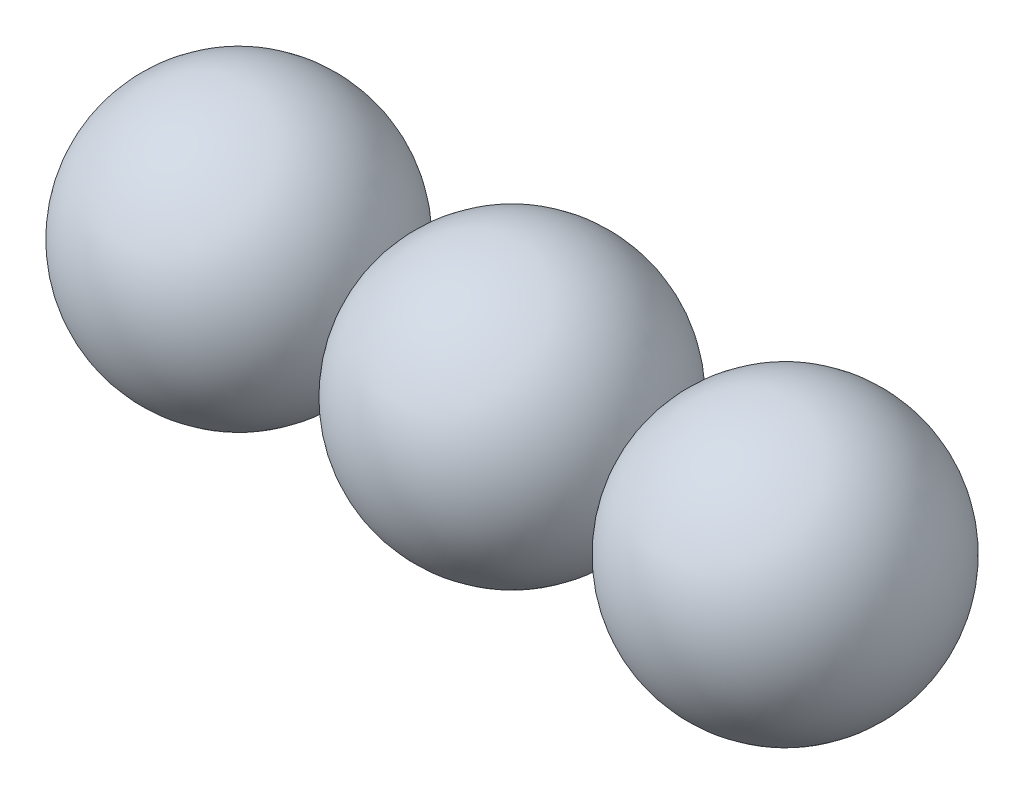
SolidWorks part; units mm, degrees
ref_plane "前基準面" through (0, 0, 0) normal (0, 0, 1) x (1, 0, 0)
ref_plane "上基準面" through (0, 0, 0) normal (0, 1, 0) x (1, 0, 0)
ref_plane "右基準面" through (0, 0, 0) normal (1, 0, 0) x (0, 0, -1)
sketch "草圖1" plane through (0, 0, 0) normal (0, 0, 1) x (1, 0, 0)
  line L0 (0, 30) -> (0, -57.2417)
  line L1 (0, 30) -> (0, -30)
  line L2 (60, 30) -> (60, -30)
  line L3 (120, 30) -> (120, -30)
  line L4 (60, 30) -> (60, -63.2368)
  line L5 (150, 0) -> (228.3593, 0)
  line L6 (60, -63.2368) -> (60, -30)
  line L7 (120, -30) -> (120, -48.9727)
  line L8 (120, -48.9727) -> (120, -30)
  arc A0 (0, -30) -> (0, 30) centre (0, 0) ccw
  arc A1 (60, -30) -> (60, 30) centre (60, 0) ccw
  arc A2 (120, -30) -> (120, 30) centre (120, 0) ccw
  dimension "D1" = 60
  dimension "D2" = 60
  dimension "D3" = 60
  dimension "D4" = 60
  dimension "D5" = 60
revolve "旋轉1" add sketch "草圖1" angle 360 about L0 region at (12.7324, 0, 0)
revolve "旋轉2" add sketch "草圖1<8>" angle 360 about L4 region at (72.7324, 0, 0)
sketch "草圖1<8>" plane through (0, 0, 0) normal (0, 0, 1) x (1, 0, 0) same geometry as "草圖1"
revolve "旋轉3" add sketch "草圖1<9>" angle 360 about L7 region at (132.7324, 0, 0)
sketch "草圖1<9>" plane through (0, 0, 0) normal (0, 0, 1) x (1, 0, 0) same geometry as "草圖1"
